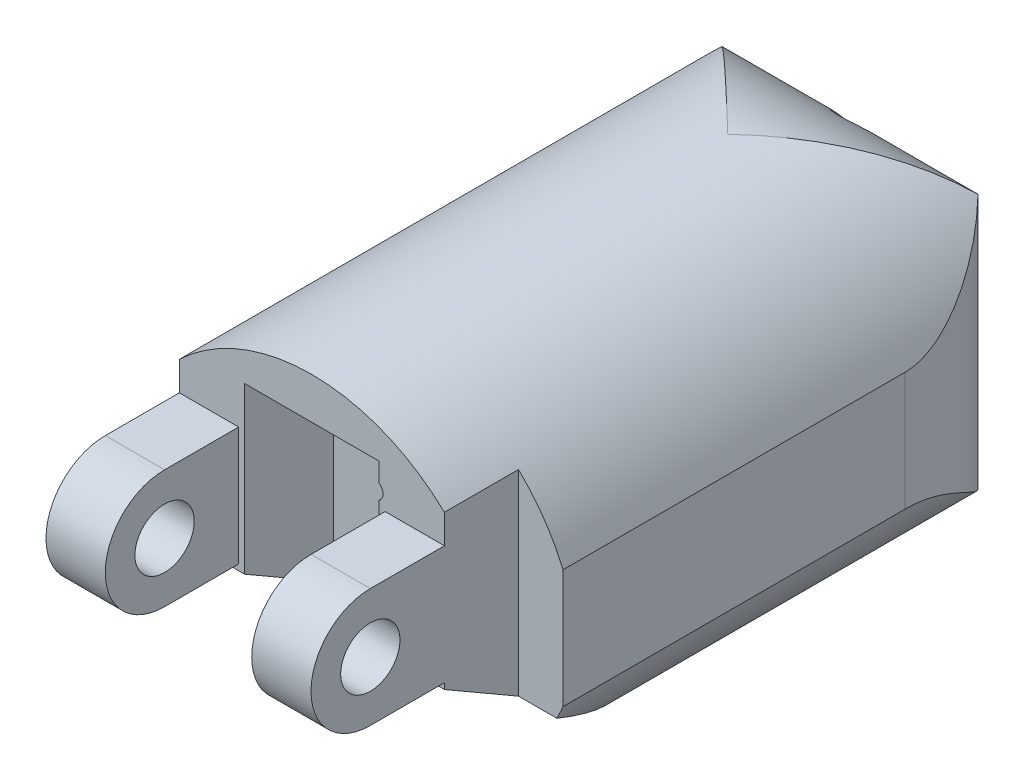
SolidWorks part; units mm, degrees
material "PET"
ref_plane "Front Plane" through (0, 0, 0) normal (0, 0, 1) x (1, 0, 0)
ref_plane "Top Plane" through (0, 0, 0) normal (0, 1, 0) x (1, 0, 0)
ref_plane "Right Plane" through (0, 0, 0) normal (1, 0, 0) x (0, 0, -1)
sketch "Sketch1" plane through (0, 0, 0) normal (0, 0, 1) x (1, 0, 0)
  line L0 (0, 0) -> (0, 5.08)
  line L3 (15.1638, 5.08) -> (15.1638, 0)
  arc A2 (0, 5.08) -> (15.1638, 5.08) centre (7.5819, 1.9002) cw
  arc A3 (0, 0) -> (15.1638, 0) centre (7.5819, 3.1798) ccw
  point P7 (7.5819, -5.0419)
  point P8 (7.5819, 10.1219)
  dimension "D1" = 15.1638
  dimension "D2" = 15.1638
  dimension "D3" = 5.08
extrude "Boss-Extrude1" add sketch "Sketch1" along normal mid plane 25.4 contours A2 L3 A3 L0
sketch "Sketch2" plane through (0, 0, 0) normal (1, 0, 0) x (0, 0, -1)
  line L4 (15.875, 2.54) -> (-49984.125, 2.54) construction
  line L5 (12.7, 5.08) -> (12.7, 0) construction
  line L6 (-12.7, 5.08) -> (-12.7, 0) construction
  line L7 (-12.7, -5.0419) -> (-12.7, 1.27)
  line L8 (-1.7675, -5.0419) -> (-12.7, -5.0419)
  line L9 (-12.7, 1.27) -> (-1.7675, -5.0419)
  line L10 (0, -1000) -> (0, 49000) construction
  line L30 (-12.7, 0) -> (-12.7, -5.0419) construction
  point P0 (-15.0884, 2.54)
  point P11 (12.7, 2.54)
  point P14 (-12.7, 2.54)
  dimension "D1" = 60
  dimension "D2" = 1.27
extrude "Cut-Extrude1" cut sketch "Sketch2" along normal through all
sketch "Sketch3" plane through (0, 0, 12.7) normal (0, 0, 1) x (1, 0, 0)
  line L3 (-4.9679, 3.175) -> (22.8791, 3.175) construction
  line L4 (15.1638, 5.08) -> (15.1638, 1.27) construction
  line L9 (7.5819, -997.6135) -> (7.5819, 49002.3865) construction
  arc A0 (15.1638, 5.08) -> (0, 5.08) centre (7.5819, 1.9002) ccw construction
  arc A3 (15.1638, 5.08) -> (0, 5.08) centre (7.5819, 1.9002) ccw
  arc A5 (13.9926, 4.5888) -> (1.1712, 4.5888) centre (7.5819, 1.9002) ccw
  arc A6 (4.9766, 8.3453) -> (10.1872, 8.3453) centre (7.5819, 10.16) ccw
  arc A7 (13.9926, 1.7612) -> (1.1712, 1.7612) centre (7.5819, 4.4498) cw
  arc A8 (4.9766, -1.9953) -> (10.1872, -1.9953) centre (7.5819, -3.81) cw
  arc A9 (13.9926, 4.5888) -> (1.1712, 4.5888) centre (7.5819, 1.9002) ccw construction
  point P14 (7.5819, 6.985)
  point P25 (15.1638, 3.175)
  dimension "D2" = 1.27
  dimension "D4" = 3.175
  dimension "D5" = 3.81
extrude "Cut-Extrude2" cut sketch "Sketch3" against normal through all contours A8 A7 region at (7.5819, -1.6392, 12.7)
ref_plane "Plane1" through (0, 0, 0) normal (0, 0, -1) x (-1, 0, 0)
ref_point "Point1"
ref_plane "Plane2" through (7.5819, 0, 0) normal (1, 0, 0) x (0, 0, -1)
sketch "Sketch4" plane through (0, 0, 0) normal (-1, 0, 0) x (0, 0, 1)
  line L0 (-12.7, -5.0419) -> (1.7675, -5.0419) construction
  line L1 (-12.7, 0) -> (-12.7, -5.0419) construction
  line L2 (-12.7, 5.08) -> (-12.7, 0) construction
  line L3 (-12.7, 10.1219) -> (-12.7, 5.08) construction
  line L4 (12.7, 10.1219) -> (-12.7, 10.1219) construction
  line L5 (-12.7, -5.0419) -> (1.7675, -5.0419)
  line L6 (-12.7, 0) -> (-12.7, -5.0419)
  line L7 (-12.7, 5.08) -> (-12.7, 0)
  line L8 (-12.7, 10.1219) -> (-12.7, 5.08)
  line L9 (12.7, 10.1219) -> (-12.7, 10.1219)
  arc A0 (-5.1181, 10.1219) -> (-5.1181, -5.0419) centre (-5.1181, 2.54) ccw
  point P9 (-12.7, 2.54)
  point P10 (-12.7, 2.54)
  line M1 (-12.7, 0) -> (10.5003, 0)
  line M3 (12.7, 5.08) -> (-12.7, 5.08)
  line M4 (-12.7, 5.08) -> (-12.7, 0)
extrude "Cut-Extrude3" cut sketch "Sketch4" against normal through all contours A0 L9 L8 M3 | A0 M3 M4 | A0 L7 M1 | A0 L6 L5 M1 region at (0, -3.4702, -10.9586) region at (0, 4.4487, -12.5692) region at (0, 0.6313, -12.5692) region at (0, 8.5502, -10.9586)
sketch "Sketch5" plane through (0, 0, 0) normal (0, 1, 0) x (1, 0, 0)
  line L0 (15.1638, 12.7) -> (0, 12.7) construction
  line L1 (15.1638, 12.2619) -> (15.1638, 12.7) construction
  line L2 (15.1638, -12.7) -> (15.1638, 12.2619) construction
  line L3 (0, -12.7) -> (0, 12.2619) construction
  line L4 (15.1638, 12.7) -> (0, 12.7)
  line L5 (15.1638, 12.2619) -> (15.1638, 12.7)
  line L6 (15.1638, -12.7) -> (15.1638, 12.2619)
  line L7 (0, -12.7) -> (0, 12.2619)
  line L8 (0, 12.2619) -> (0, 12.7)
  arc A0 (0, 5.1181) -> (15.1638, 5.1181) centre (7.5819, 5.1181) cw
  point P9 (7.5819, 12.7)
  point P10 (7.5819, 12.7)
extrude "Cut-Extrude4" cut sketch "Sketch5" against normal through all both and the other way through all contours L4 A0 L6 L5 | L7 A0 L4 L8 region at (13.4702, 0, -11.0064) region at (1.6936, 0, -11.0064)
ref_plane "Plane3" through (2.54, 0, 0) normal (1, 0, 0) x (0, 0, -1)
ref_plane "Plane4" through (12.6238, 0, 0) normal (1, 0, 0) x (0, 0, -1)
sketch "Sketch8" plane through (2.54, 0, 0) normal (1, 0, 0) x (0, 0, -1)
  line L0 (-12.7, 6.604) -> (-15.875, 6.604)
  line L1 (-12.7, 5.08) -> (-12.7, 1.27) construction
  line L2 (-12.7, 6.604) -> (-12.7, 1.524)
  line L3 (-12.7, 1.524) -> (-15.875, 1.524)
  line L4 (-12.7, 5.08) -> (-12.7, 0) construction
  line L5 (-10.5003, 0) -> (5.1181, 0) construction
  line L6 (-12.7, 1.524) -> (-12.7, 0) construction
  line L7 (-12.7, 0) -> (-16.1427, 0) construction
  arc A0 (-15.875, 6.604) -> (-15.875, 1.524) centre (-15.875, 4.064) ccw
  circle A1 centre (-15.875, 4.064) radius 1.27
  dimension "D1" = 2.54
  dimension "D2" = 5.08
  dimension "D3" = 3.175
  dimension "D4" = 4.064
extrude "Boss-Extrude3" add sketch "Sketch8" along normal mid plane 1.27
ref_plane "Plane5" through (7.5819, 0, 0) normal (1, 0, 0) x (0, 0, -1)
sketch "Sketch10" plane through (1.905, 0, 0) normal (-1, 0, 0) x (0, 0, 1)
  line L3 (12.7, 6.604) -> (12.7, 1.524)
  line L4 (12.7, 1.524) -> (15.875, 1.524)
  line L5 (15.875, 6.604) -> (12.7, 6.604)
  line L6 (12.7, 6.604) -> (12.7, 1.524)
  line L7 (12.7, 1.524) -> (15.875, 1.524)
  line L8 (15.875, 6.604) -> (12.7, 6.604)
  circle A0 centre (15.875, 4.064) radius 1.27 construction
  arc A1 (15.875, 1.524) -> (15.875, 6.604) centre (15.875, 4.064) ccw
  arc A2 (15.875, 1.524) -> (15.875, 6.604) centre (15.875, 4.064) ccw
  circle A3 centre (15.875, 4.064) radius 1.27
  dimension "D1" = 0
extrude "Boss-Extrude4" add sketch "Sketch10" along normal blind 1.27
mirror "Mirror1" about plane through (7.5819, 0, 0) normal (1, 0, 0) of "Boss-Extrude4", "Boss-Extrude3"
sketch "Sketch11" plane through (0.635, 0, 0) normal (-1, 0, 0) x (0, 0, 1)
  line L3 (15.875, 6.604) -> (12.7, 6.604)
  line L4 (12.7, 6.2976) -> (12.7, 1.524)
  line L5 (12.7, 1.524) -> (15.875, 1.524)
  line L6 (15.875, 6.604) -> (12.7, 6.604)
  line L7 (12.7, 6.2976) -> (12.7, 1.524)
  line L8 (12.7, 1.524) -> (15.875, 1.524)
  line L10 (12.7, 6.604) -> (12.7, 6.2976)
  line L11 (12.7, 6.604) -> (12.7, 6.2976)
  circle A0 centre (15.875, 4.064) radius 1.27 construction
  circle A1 centre (15.875, 4.064) radius 1.27
  arc A3 (15.875, 1.524) -> (15.875, 6.604) centre (15.875, 4.064) ccw
  arc A4 (15.875, 1.524) -> (15.875, 6.604) centre (15.875, 4.064) ccw
  dimension "D1" = 0
extrude "Cut-Extrude6" cut sketch "Sketch11" against normal blind 1.27
sketch "Sketch12" plane through (3.175, 0, 0) normal (1, 0, 0) x (0, 0, -1)
  line L3 (-12.7, 1.524) -> (-12.7, 6.604)
  line L4 (-12.7, 6.604) -> (-15.875, 6.604)
  line L5 (-15.875, 1.524) -> (-12.7, 1.524)
  line L6 (-12.7, 1.524) -> (-12.7, 6.604)
  line L7 (-12.7, 6.604) -> (-15.875, 6.604)
  line L8 (-15.875, 1.524) -> (-12.7, 1.524)
  circle A0 centre (-15.875, 4.064) radius 1.27 construction
  arc A1 (-15.875, 6.604) -> (-15.875, 1.524) centre (-15.875, 4.064) ccw
  arc A2 (-15.875, 6.604) -> (-15.875, 1.524) centre (-15.875, 4.064) ccw
  circle A3 centre (-15.875, 4.064) radius 1.27
  dimension "D1" = 0
extrude "Boss-Extrude5" add sketch "Sketch12" along normal blind 1.27
mirror "Mirror2" about plane through (7.5819, 0, 0) normal (1, 0, 0) of "Cut-Extrude6", "Boss-Extrude5"
sketch "Sketch13" plane through (0, 0, 12.7) normal (0, 0, 1) x (1, 0, 0)
  line L1 (0, -5.0419) -> (1.905, -5.0419)
  line L2 (0, -5.0419) -> (0, 7.8474)
  line L3 (0, 7.8474) -> (1.905, 7.8474)
  line L4 (1.905, -5.0419) -> (1.905, 7.8474)
  line L5 (7.5819, 0.762) -> (7.5819, 14.3113) construction
  line L6 (1.905, 6.604) -> (1.905, 1.524) construction
  line L7 (13.2588, -5.0419) -> (13.2588, 7.8474)
  line L8 (15.1638, 7.8474) -> (13.2588, 7.8474)
  line L9 (15.1638, -5.0419) -> (15.1638, 7.8474)
  line L10 (15.1638, -5.0419) -> (13.2588, -5.0419)
  line L11 (3.2723, -5.0419) -> (13.6472, -5.0419) construction
  line L12 (0, 1.27) -> (0, 5.08) construction
  line L14 (4.445, 0.762) -> (10.7188, 0.762) construction
  line L15 (10.7188, 1.524) -> (10.7188, 6.604) construction
  line L17 (4.445, 1.524) -> (4.445, 6.604) construction
  arc A0 (0, 0) -> (15.1638, 0) centre (7.5819, 3.1798) ccw construction
  arc A1 (15.1638, 5.08) -> (0, 5.08) centre (7.5819, 1.9002) ccw construction
extrude "Cut-Extrude7" cut sketch "Sketch13" against normal blind 3.175
sketch "Sketch14" plane through (0, 0, 12.7) normal (0, 0, 1) x (1, 0, 0)
  line L0 (4.699, -1.9953) -> (10.4648, -1.9953)
  line L5 (4.699, 8.3453) -> (10.4648, 8.3453)
  line L9 (4.699, -1.9953) -> (4.699, 8.3453)
  line L11 (10.4648, 8.3453) -> (10.4648, -1.9953)
  line L12 (4.445, 1.524) -> (4.445, 6.604) construction
  line L13 (10.7188, 6.604) -> (10.7188, 1.524) construction
  line M13 (1.905, 1.27) -> (13.2588, 1.27)
  dimension "D1" = 0.254
  dimension "D2" = 0.254
extrude "Cut-Extrude8" cut sketch "Sketch14" against normal blind 3.81 contours M13 | L11 L0 L9 L5 region at (7.5819, -0.3626, 12.7)
sketch "Sketch18" plane through (0, 0, 0) normal (0, 1, 0) x (1, 0, 0)
  circle A1 centre (7.5819, 10.8331) radius 0.9525
  arc A2 (13.0668, 10.3527) -> (7.5819, 12.7) centre (7.5819, 5.1181) ccw construction
  dimension "D1" = 1.905
  dimension "D2" = 5.715
extrude "Cut-Extrude12" cut sketch "Sketch18" against normal blind 1.27 and the other way through all
sketch "Sketch19" plane through (0, 0, 0) normal (-1, 0, 0) x (0, 0, 1)
  text T0 "Point1"
extrude "Cut-Extrude13" cut sketch "Sketch19" against normal blind 1
sketch "Sketch20" plane through (0, 0, 8.89) normal (0, 0, 1) x (1, 0, 0)
  line L0 (4.699, 8.3453) -> (10.4648, 8.3453) construction
  line L1 (4.9149, 1.905) -> (10.2489, 1.905)
  line L2 (4.9149, 1.905) -> (4.9149, 7.5946)
  line L3 (4.9149, 7.5946) -> (10.2489, 7.5946) construction
  line L4 (10.2489, 1.905) -> (10.2489, 7.5946) construction
  line L5 (4.9149, 1.905) -> (10.2489, 7.5946) construction
  line L6 (4.9149, 7.5946) -> (10.2489, 1.905) construction
  line L7 (4.699, 8.3453) -> (10.4648, 8.3453)
  line L8 (9.6139, 7.2136) -> (10.2489, 7.2136) construction
  line L9 (9.6139, 7.5946) -> (10.2489, 7.5946)
  line L10 (9.6139, 6.8326) -> (10.2489, 6.8326)
  arc A0 (9.6139, 7.5946) -> (9.6139, 6.8326) centre (9.6139, 7.2136) ccw
  arc A1 (10.2489, 6.8326) -> (10.2489, 7.5946) centre (10.2489, 7.2136) ccw
  point P0 (7.5819, 4.7498)
  point P8 (7.5819, 7.5946)
  point P9 (7.5819, 8.3453)
  point P12 (9.9314, 7.2136)
  line M6 (10.4648, -0.9297) -> (10.4648, 8.3453)
  dimension "D1" = 5.6896
  dimension "D2" = 5.334
  dimension "D3" = 1.905
  dimension "D4" = 0.635
  dimension "D5" = 0.762
extrude "Cut-Extrude14" cut sketch "Sketch20" against normal blind 17.78 and the other way up to surface (3.81 mm away) contours A1 L9 A0 L10 M6 | A1 M6 region at (9.881, 7.2136, 8.89) region at (10.5322, 7.2136, 8.89) other way up to face at (7.5819, 4.5157, 12.7)
fillet "Fillet1" radius 1.27 1 edges at (7.7543, -0.6397, -9.8963)
equation "\"D1@Sketch1\"=0.597"
equation "\"D2@Sketch1\"=0.597"
equation "\"D1@Boss-Extrude1\"=1"
